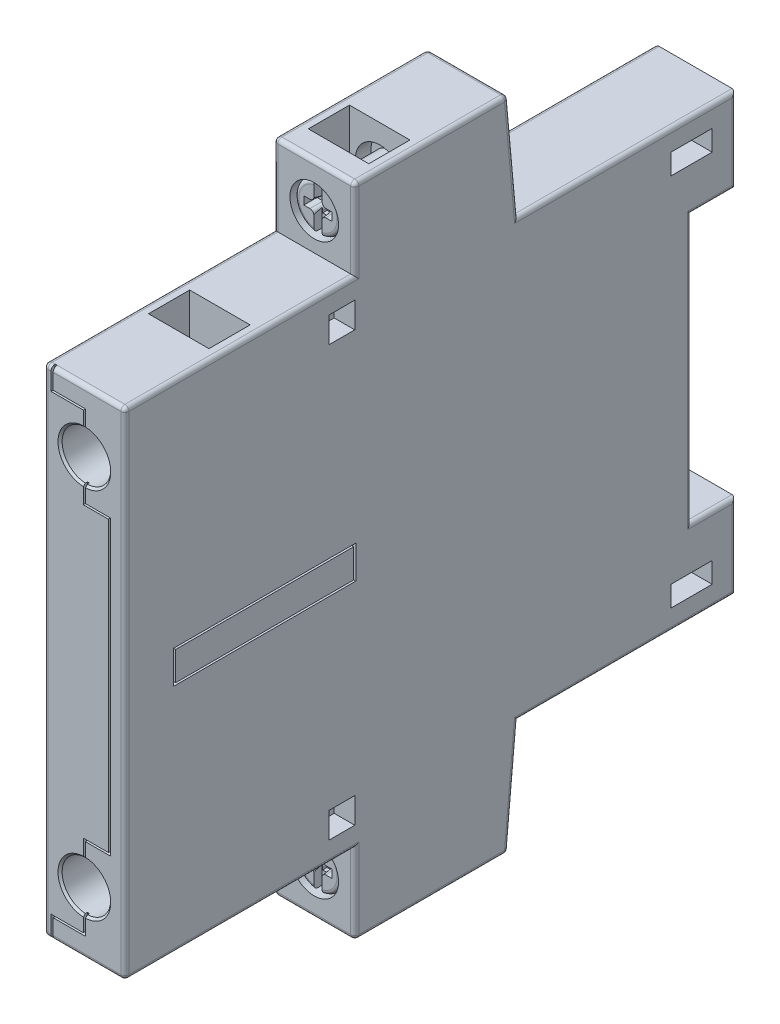
SolidWorks part; units mm, degrees
ref_plane "Front Plane" through (0, 0, 0) normal (0, 0, 1) x (1, 0, 0)
ref_plane "Top Plane" through (0, 0, 0) normal (0, 1, 0) x (1, 0, 0)
ref_plane "Right Plane" through (0, 0, 0) normal (1, 0, 0) x (0, 0, -1)
sketch "Sketch1" plane through (0, 0, 0) normal (1, 0, 0) x (0, 0, -1)
  line L0 (-37.7165, -30.5994) -> (-37.7165, 30.5994) construction
  line L1 (37.7165, -26.9011) -> (37.7165, -16.4998) construction
  line L2 (-37.7165, 0) -> (37.7165, 0) construction
  line L3 (-37.7165, -30.5994) -> (-9.3472, -30.5994) construction
  line L4 (-9.3472, -30.5994) -> (-9.3472, -40.5003) construction
  line L5 (-9.3472, -40.5003) -> (9.6012, -40.5003) construction
  line L6 (9.6012, -40.5003) -> (10.8412, -26.9011) construction
  line L7 (10.8412, -26.9011) -> (37.7165, -26.9011) construction
  line L8 (37.7165, -16.4998) -> (32.2174, -16.4998) construction
  line L9 (32.2174, -16.4998) -> (32.2174, 16.4998) construction
  line L10 (0, -40.5003) -> (0, 40.5003) construction
  line L11 (-37.7165, 30.5994) -> (-9.3472, 30.5994) construction
  line L12 (-9.3472, 30.5994) -> (-9.3472, 40.5003) construction
  line L13 (-9.3472, 40.5003) -> (9.6012, 40.5003) construction
  line L14 (9.6012, 40.5003) -> (10.8412, 26.9011) construction
  line L15 (10.8412, 26.9011) -> (37.7165, 26.9011) construction
  line L16 (37.7165, 26.9011) -> (37.7165, 16.4998) construction
  line L17 (37.7165, 16.4998) -> (32.2174, 16.4998) construction
  point P3 (-37.7165, 0)
  point P6 (37.7165, 0)
  point P10 (0, 0)
  point P19 (0, 0)
  point P26 (32.2174, 0)
  dimension "D2" = 61.1988
  dimension "Depth" = 75.4329
  dimension "D3" = 28.3693
  dimension "D4" = 26.9011
  dimension "D5" = 5.4991
  dimension "D6" = 18.9484
  dimension "D7" = 95.21
  dimension "Height" = 81.0006
  dimension "D9" = 16.4998
sketch "Sketch2" plane through (0, 0, 0) normal (0, 0, 1) x (1, 0, 0)
  line L0 (-5, 0) -> (5, 0) construction
  line L2 (0, -22.9997) -> (0, 22.9997) construction
  line L3 (0, -35.1155) -> (0, 35.1155) construction
  line L4 (0, 40.5003) -> (0, 26.9011) construction
  circle A0 centre (0, 35.1155) radius 2.9997 construction
  circle A1 centre (0, 22.9997) radius 2.9997 construction
  circle A2 centre (0, -22.9997) radius 2.9997 construction
  circle A3 centre (0, -35.1155) radius 2.9997 construction
  point P4 (0, 0)
  point P8 (0, 0)
  point P14 (0, 0)
  dimension "D4" = 5.9995
  dimension "Width" = 10
  dimension "D2" = 45.9994
  dimension "D3" = 70.231
sketch "Sketch3" plane through (0, 0, 0) normal (1, 0, 0) x (0, 0, -1)
  line L0 (-37.7165, -30.5994) -> (-37.7165, 30.5994) construction
  line L1 (-37.7165, 30.5994) -> (-9.3472, 30.5994) construction
  line L2 (-9.3472, 30.5994) -> (-9.3472, 40.5003) construction
  line L3 (-9.3472, 40.5003) -> (9.6012, 40.5003) construction
  line L4 (9.6012, 40.5003) -> (10.8412, 26.9011) construction
  line L5 (10.8412, 26.9011) -> (37.7165, 26.9011) construction
  line L6 (37.7165, 26.9011) -> (37.7165, 16.4998) construction
  line L7 (37.7165, 16.4998) -> (32.2174, 16.4998) construction
  line L8 (32.2174, -16.4998) -> (32.2174, 16.4998) construction
  line L9 (37.7165, -16.4998) -> (32.2174, -16.4998) construction
  line L10 (37.7165, -26.9011) -> (37.7165, -16.4998) construction
  line L11 (10.8412, -26.9011) -> (37.7165, -26.9011) construction
  line L12 (9.6012, -40.5003) -> (10.8412, -26.9011) construction
  line L13 (-9.3472, -40.5003) -> (9.6012, -40.5003) construction
  line L14 (-9.3472, -30.5994) -> (-9.3472, -40.5003) construction
  line L15 (-37.7165, -30.5994) -> (-9.3472, -30.5994) construction
  line L16 (-37.7165, -30.5994) -> (-37.7165, 30.5994)
  line L17 (-37.7165, 30.5994) -> (-9.3472, 30.5994)
  line L18 (-9.3472, 30.5994) -> (-9.3472, 40.5003)
  line L19 (-9.3472, 40.5003) -> (9.6012, 40.5003)
  line L20 (9.6012, 40.5003) -> (10.8412, 26.9011)
  line L21 (10.8412, 26.9011) -> (37.7165, 26.9011)
  line L22 (37.7165, 26.9011) -> (37.7165, 16.4998)
  line L23 (37.7165, 16.4998) -> (32.2174, 16.4998)
  line L24 (32.2174, -16.4998) -> (32.2174, 16.4998)
  line L25 (37.7165, -16.4998) -> (32.2174, -16.4998)
  line L26 (37.7165, -26.9011) -> (37.7165, -16.4998)
  line L27 (10.8412, -26.9011) -> (37.7165, -26.9011)
  line L28 (9.6012, -40.5003) -> (10.8412, -26.9011)
  line L29 (-9.3472, -40.5003) -> (9.6012, -40.5003)
  line L30 (-9.3472, -30.5994) -> (-9.3472, -40.5003)
  line L31 (-37.7165, -30.5994) -> (-9.3472, -30.5994)
extrude "Boss-Extrude1" add sketch "Sketch3" along normal up to vertex (5 mm away) and the other way up to vertex (5 mm away) up to point (5, 0, 0) other way up to point (-5, 0, 0)
fillet "Fillet5" radius 0.508 38 edges at (5, 30.5994, 23.5318) (5, 35.5498, 9.3472) (5, 40.5003, -0.127) (5, 33.7007, -10.2212) (5, 26.9011, -24.2788) (5, 21.7005, -37.7165) (5, 16.4998, -34.9669) (5, 0, -32.2174) (5, -16.4998, -34.9669) (5, -21.7005, -37.7165) (5, -26.9011, -24.2788) (5, -33.7007, -10.2212) (5, -40.5003, -0.127) (5, -35.5498, 9.3472) (5, -30.5994, 23.5318) (5, 0, 37.7165) (0, -30.5994, 37.7165) (0, 30.5994, 37.7165) (-5, -35.5498, 9.3472) (-5, -40.5003, -0.127) (-5, -33.7007, -10.2212) (-5, -26.9011, -24.2788) (-5, -21.7005, -37.7165) (-5, -16.4998, -34.9669) (-5, 0, -32.2174) (-5, 16.4998, -34.9669) (-5, 21.7005, -37.7165) (-5, 26.9011, -24.2788) (-5, 33.7007, -10.2212) (-5, 40.5003, -0.127) (-5, 35.5498, 9.3472) (-5, 30.5994, 23.5318) (-5, 0, 37.7165) (-5, -30.5994, 23.5318) (0, -40.5003, -9.6012) (0, -40.5003, 9.3472) (0, 40.5003, -9.6012) (0, 40.5003, 9.3472)
sketch "Sketch5" plane through (0, 0, 37.7165) normal (0, 0, 1) x (1, 0, 0)
  circle A0 centre (0, -22.9997) radius 2.9997 construction
  circle A1 centre (0, 22.9997) radius 2.9997 construction
  circle A2 centre (0, -22.9997) radius 2.9997
  circle A3 centre (0, 22.9997) radius 2.9997
extrude "Cut-Extrude1" cut sketch "Sketch5" against normal blind 10
sketch "Sketch6" plane through (0, 0, 9.3472) normal (0, 0, 1) x (1, 0, 0)
  circle A0 centre (0, -35.1155) radius 2.9997 construction
  circle A1 centre (0, 35.1155) radius 2.9997 construction
  circle A2 centre (0, -35.1155) radius 2.9997
  circle A3 centre (0, 35.1155) radius 2.9997
extrude "Cut-Extrude2" cut sketch "Sketch6" against normal blind 10
sketch "Sketch7" plane through (0, 30.5994, 0) normal (0, 1, 0) x (1, 0, 0)
  line L0 (0, -37.7165) -> (0, -9.3472) construction
  line L1 (-3.73, -26.0718) -> (3.73, -26.0718)
  line L2 (-3.73, -26.0718) -> (-3.73, -20.9918)
  line L3 (-3.73, -20.9918) -> (3.73, -20.9918)
  line L4 (3.73, -26.0718) -> (3.73, -20.9918)
  line L5 (-3.73, -26.0718) -> (3.73, -20.9918) construction
  line L6 (-3.73, -20.9918) -> (3.73, -26.0718) construction
  line L7 (5, -9.3472) -> (5, -37.7165) construction
  point P0 (0, -23.5318)
  point P9 (5, -23.5318)
  dimension "D1" = 1.27
  dimension "D2" = 5.08
extrude "Cut-Extrude3" cut sketch "Sketch7" against normal blind 12.7
sketch "Sketch8" plane through (0, 40.5003, 0) normal (0, 1, 0) x (1, 0, 0)
  line L0 (0, -9.3472) -> (0, 9.6012) construction
  line L1 (-3.73, -6.35) -> (3.73, -6.35)
  line L2 (-3.73, -6.35) -> (-3.73, -1.27)
  line L3 (-3.73, -1.27) -> (3.73, -1.27)
  line L4 (3.73, -6.35) -> (3.73, -1.27)
  line L5 (-3.73, -6.35) -> (3.73, -1.27) construction
  line L6 (-3.73, -1.27) -> (3.73, -6.35) construction
  line L7 (3.73, -26.0718) -> (3.73, -20.9918) construction
  line L8 (-2.9997, 0) -> (2.9997, 0) construction
  point P0 (0, -3.81)
  dimension "D1" = 1.27
extrude "Cut-Extrude4" cut sketch "Sketch8" against normal blind 12.7
mirror "Mirror1" about plane through (0, 0, 0) normal (0, 1, 0) of "Cut-Extrude4", "Cut-Extrude3"
sketch "Sketch9" plane through (0, 0, 27.7165) normal (0, 0, 1) x (1, 0, 0)
  circle A2 centre (0, 22.9997) radius 2.8727
  circle A3 centre (0, 22.9997) radius 2.8727
  dimension "D1" = 0.127
extrude "Boss-Extrude2" add sketch "Sketch9" along normal blind 3.81 separate body
sketch "Sketch10" plane through (0, 0, 6.35) normal (0, 0, -1) x (-1, 0, 0)
  circle A2 centre (0, 35.1155) radius 2.8727
  circle A3 centre (0, 35.1155) radius 2.8727
  dimension "D1" = 0.127
extrude "Boss-Extrude3" add sketch "Sketch10" against normal blind 2.54 and the other way blind 1.27 separate body
fillet "Fillet1" radius 0.508 1 edges at (0, 37.9882, 8.89)
fillet "Fillet2" radius 0.508 1 edges at (2.8727, 22.9997, 31.5265)
sketch "Sketch11" plane through (0, 0, 31.5265) normal (0, 0, 1) x (1, 0, 0)
  line L0 (0, 25.8724) -> (0, 20.127)
  line L1 (0, 26.9011) -> (0, 16.4998) construction
  circle A0 centre (0, 22.9997) radius 2.8727 construction
extrude "Cut-Extrude-Thin1" cut sketch "Sketch11" against normal blind 1 thin thin type mid plane wall 1
sketch "Sketch12" plane through (0, 0, 31.5265) normal (0, 0, 1) x (1, 0, 0)
  line L0 (-1.75, 22.9997) -> (1.75, 22.9997)
  line L1 (0, 26.9011) -> (0, 16.4998) construction
  line L2 (0, 21.7497) -> (0, 24.2497)
  point P4 (0, 22.9997)
  point P10 (0, 22.9997)
  dimension "D1" = 3.5
  dimension "D2" = 2.5
extrude "Cut-Extrude-Thin2" cut sketch "Sketch12" against normal blind 1.5 draft 5 thin thin type mid plane wall 1
fillet "Fillet3" radius 0.508 4 edges at (-0.3906, 22.6091, 30.2765) (0.3906, 22.6091, 30.2765) (0.3906, 23.3903, 30.2765) (-0.3906, 23.3903, 30.2765)
sketch "Sketch13" plane through (0, 0, 8.89) normal (0, 0, 1) x (1, 0, 0)
  line L0 (0, 32.2428) -> (0, 37.9882)
  line L1 (0, 40.5003) -> (0, 26.9011) construction
  circle A0 centre (0, 35.1155) radius 2.8727 construction
  point P6 (0, 35.1155)
extrude "Cut-Extrude-Thin3" cut sketch "Sketch13" against normal blind 1 thin thin type mid plane wall 1
sketch "Sketch14" plane through (0, 0, 8.89) normal (0, 0, 1) x (1, 0, 0)
  line L0 (-1.75, 35.1155) -> (1.75, 35.1155)
  line L1 (0, 33.8655) -> (0, 36.3655)
  line L2 (0, 40.5003) -> (0, 26.9011) construction
  point P4 (0, 35.1155)
  point P10 (0, 35.1155)
  dimension "D1" = 2.5
  dimension "D2" = 3.5
extrude "Cut-Extrude-Thin4" cut sketch "Sketch14" against normal blind 1.4986 draft 5 thin thin type mid plane wall 1
fillet "Fillet4" radius 0.508 4 edges at (-0.3907, 34.7248, 7.6407) (0.3907, 35.5062, 7.6407) (0.3907, 34.7248, 7.6407) (-0.3907, 35.5062, 7.6407)
sketch "Sketch15" plane through (0, 0, 5.08) normal (0, 0, -1) x (-1, 0, 0)
  circle A2 centre (0, 35.1155) radius 1.8567
  circle A3 centre (0, 35.1155) radius 1.8567
  dimension "D1" = 1.016
extrude "Boss-Extrude4" add sketch "Sketch15" along normal blind 5
sketch "Sketch16" plane through (0, 0, 27.7165) normal (0, 0, -1) x (-1, 0, 0)
  circle A2 centre (0, 22.9997) radius 1.8567
  circle A3 centre (0, 22.9997) radius 1.8567
  dimension "D1" = 1.016
extrude "Boss-Extrude5" add sketch "Sketch16" along normal blind 5
sketch "Sketch17" plane through (-5, 0, 0) normal (-1, 0, 0) x (0, 0, 1)
  line L0 (37.7165, 0) -> (-37.7165, 0) construction
  line L1 (9.3472, -1.905) -> (31.5722, -1.905) construction
  line L2 (9.3472, -1.905) -> (9.3472, 1.905) construction
  line L3 (9.3472, 1.905) -> (31.5722, 1.905) construction
  line L4 (31.5722, -1.905) -> (31.5722, 1.905) construction
  line L5 (9.3472, -1.905) -> (31.5722, 1.905) construction
  line L6 (9.3472, 1.905) -> (31.5722, -1.905) construction
  line L7 (37.7165, 0) -> (-37.7165, 0) construction
  line L8 (9.3472, 28.0594) -> (12.5222, 28.0594)
  line L9 (9.3472, 28.0594) -> (9.3472, 24.8844)
  line L10 (9.3472, 24.8844) -> (12.5222, 24.8844)
  line L11 (12.5222, 28.0594) -> (12.5222, 24.8844)
  line L12 (9.3472, 28.0594) -> (12.5222, 24.8844) construction
  line L13 (9.3472, 24.8844) -> (12.5222, 28.0594) construction
  line L18 (37.7165, 30.5994) -> (9.3472, 30.5994) construction
  line L19 (-32.2174, -16.4998) -> (-32.2174, 16.4998) construction
  line L20 (-34.7574, 24.3611) -> (-29.6774, 24.3611)
  line L21 (-34.7574, 24.3611) -> (-34.7574, 21.8211)
  line L22 (-34.7574, 21.8211) -> (-29.6774, 21.8211)
  line L23 (-29.6774, 24.3611) -> (-29.6774, 21.8211)
  line L24 (-34.7574, 24.3611) -> (-29.6774, 21.8211) construction
  line L25 (-34.7574, 21.8211) -> (-29.6774, 24.3611) construction
  line L26 (-10.8412, 26.9011) -> (-37.7165, 26.9011) construction
  line L27 (-34.7574, -21.8211) -> (-29.6774, -24.3611) construction
  line L28 (-34.7574, -24.3611) -> (-29.6774, -21.8211) construction
  line L29 (9.3472, -24.8844) -> (12.5222, -28.0594) construction
  line L30 (9.3472, -28.0594) -> (12.5222, -24.8844) construction
  line L31 (-29.6774, -24.3611) -> (-29.6774, -21.8211)
  line L32 (-34.7574, -21.8211) -> (-29.6774, -21.8211)
  line L33 (-34.7574, -24.3611) -> (-34.7574, -21.8211)
  line L34 (-34.7574, -24.3611) -> (-29.6774, -24.3611)
  line L35 (12.5222, -28.0594) -> (12.5222, -24.8844)
  line L36 (9.3472, -24.8844) -> (12.5222, -24.8844)
  line L37 (9.3472, -28.0594) -> (9.3472, -24.8844)
  line L38 (9.3472, -28.0594) -> (12.5222, -28.0594)
  line L39 (9.3472, 30.5994) -> (9.3472, 40.5003) construction
  point P0 (20.4597, 0)
  point P7 (10.9347, 26.4719)
  point P15 (-32.2174, 23.0911)
  point P35 (-32.2174, -23.0911)
  point P36 (10.9347, -26.4719)
  dimension "D1" = 3.81
  dimension "D2" = 22.225
  dimension "D3" = 3.175
  dimension "D4" = 3.175
  dimension "D5" = 2.54
  dimension "D6" = 5.08
  dimension "D7" = 2.54
  dimension "D8" = 2.54
extrude "Cut-Extrude5" cut sketch "Sketch17" against normal blind 2.54
sketch "Sketch20" plane through (-5, 0, 0) normal (-1, 0, 0) x (0, 0, 1)
  line L0 (9.3472, 1.905) -> (31.5722, 1.905) construction
  line L1 (9.3472, 1.905) -> (31.5722, 1.905)
  line L2 (9.3472, -1.905) -> (9.3472, 1.905) construction
  line L3 (9.3472, -1.905) -> (31.5722, -1.905) construction
  line L4 (31.5722, -1.905) -> (31.5722, 1.905) construction
  line L5 (9.3472, -1.905) -> (9.3472, 1.905)
  line L6 (9.3472, -1.905) -> (31.5722, -1.905)
  line L7 (31.5722, -1.905) -> (31.5722, 1.905)
extrude "Cut-Extrude-Thin5" cut sketch "Sketch20" against normal blind 2.54 thin thin type mid plane wall 0.254
mirror "Mirror2" about plane through (0, 0, 0) normal (1, 0, 0) of "Cut-Extrude-Thin5", "Cut-Extrude5"
mirror "Mirror3" about plane through (0, 0, 0) normal (0, 1, 0) of bodies 116 117
chamfer "Chamfer1" distance 0.254 angle 45 2 edges at (2.9997, -22.9997, 37.7165) (2.9997, 22.9997, 37.7165)
sketch "Sketch21" plane through (0, 0, 37.7165) normal (0, 0, 1) x (1, 0, 0)
  line L0 (-3.984, -30.5994) -> (-3.984, -28.0594)
  line L1 (0, 17.94) -> (3.095, 17.94)
  line L2 (-3.984, -28.0594) -> (0, -28.0594)
  line L3 (0, -28.0594) -> (0, -17.94)
  line L4 (0, -17.94) -> (3.095, -17.94)
  line L5 (3.095, -17.94) -> (3.095, 17.94)
  line L6 (4.492, -30.5994) -> (-4.492, -30.5994) construction
  line L7 (-5, -30.0914) -> (-5, 30.0914) construction
  line L8 (-5, 0) -> (5, 0) construction
  line L9 (-5, 0) -> (5, 0) construction
  line L10 (0, 28.0594) -> (0, 17.94)
  line L11 (-3.984, 28.0594) -> (0, 28.0594)
  line L12 (-3.984, 30.5994) -> (-3.984, 28.0594)
  point P13 (0, -22.9997)
  point P20 (3.095, 0)
  dimension "D1" = 1.016
  dimension "D2" = 2.54
  dimension "D3" = 1.905
extrude "Cut-Extrude-Thin6" cut sketch "Sketch21" against normal up to vertex (0.508 mm away) and the other way through all thin up to point (-4.492, 30.5994, 37.2085) thin type mid plane wall 0.254
